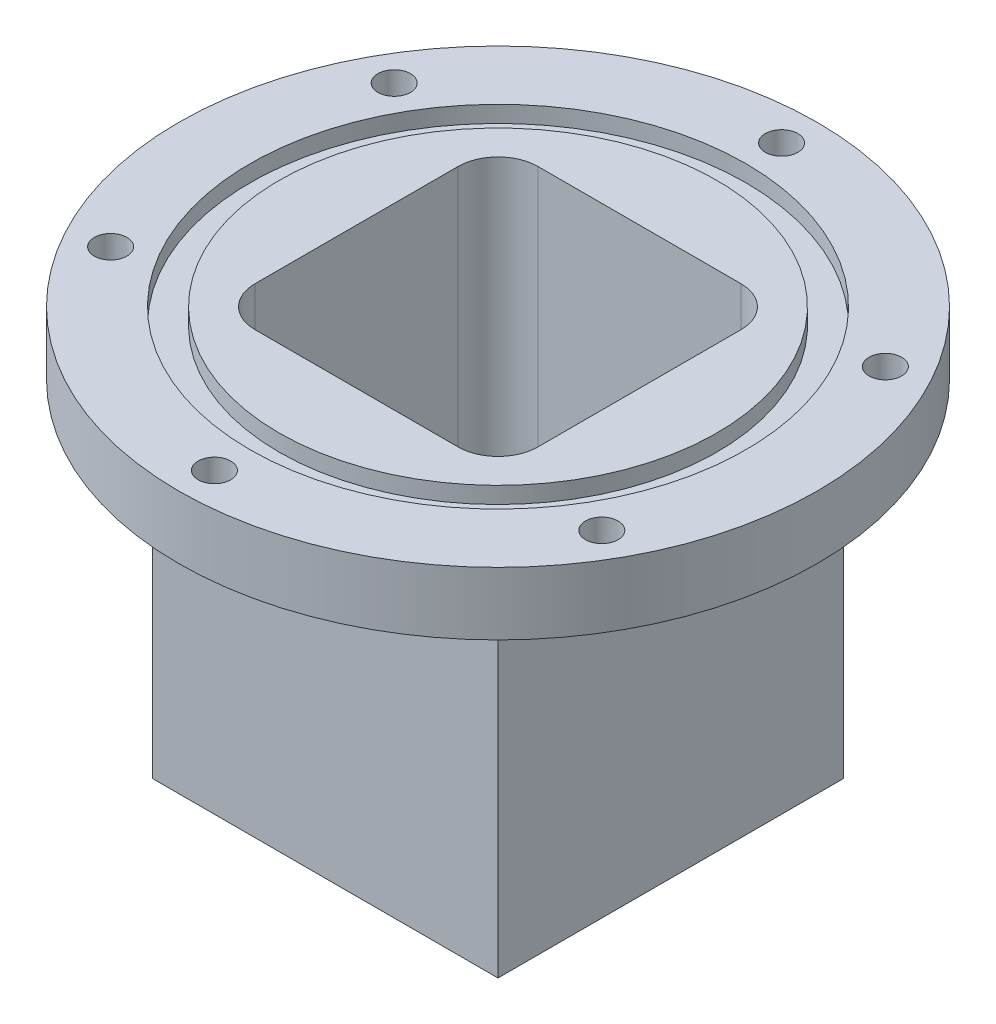
SolidWorks part; units mm, degrees
note: '?' marks a value the reader was unsure of. The reader was unsure of these and kept them because the rebuilt part matched: shared geometry of "Sketch1<3>".
ref_plane "Front Plane" through (0, 0, 0) normal (0, 0, 1) x (1, 0, 0)
ref_plane "Top Plane" through (0, 0, 0) normal (0, 1, 0) x (1, 0, 0)
ref_plane "Right Plane" through (0, 0, 0) normal (1, 0, 0) x (0, 0, -1)
ref_axis "Axis1" through (0, 47.5, 0) along (0, -1, 0)?
sketch "Sketch1" plane through (0, 0, 0) normal (0, 1, 0) x (1, 0, 0)
  line L0 (27.5, 27.5) -> (-27.5, 27.5)
  line L1 (22.5, -22.5) -> (-22.5, -22.5)
  line L2 (22.5, -22.5) -> (22.5, 22.5)
  line L3 (22.5, 22.5) -> (-22.5, 22.5)
  line L4 (-22.5, -22.5) -> (-22.5, 22.5)
  line L5 (22.5, -22.5) -> (-22.5, 22.5) construction
  line L6 (22.5, 22.5) -> (-22.5, -22.5) construction
  line L7 (-27.5, -27.5) -> (-27.5, 27.5)
  line L8 (27.5, -27.5) -> (-27.5, -27.5)
  line L9 (27.5, -27.5) -> (27.5, 27.5)
  point P0 (0, 0)
  dimension "D1" = 45
  dimension "D2" = 5
extrude "Boss-Extrude1" add sketch "Sketch1" against normal blind 5 contours L4 L1 L2 L3 | L8 L9 L0 L7 L1 L4 L3 L2
extrude "Boss-Extrude2" add sketch "Sketch1<3>" along normal blind 60 contours L8 L9 L0 L7 L1 L4 L3 L2
sketch "Sketch1<3>" plane through (0, 0, 0) normal (0, 1, 0) x (1, 0, 0) same geometry as "Sketch1"
sketch "Sketch6" plane through (0, 60, 0) normal (0, 1, 0) x (1, 0, 0)
  line L1 (35.921, -35.921) -> (-35.921, -35.921) construction
  line L2 (35.921, -35.921) -> (35.921, 35.921) construction
  line L3 (35.921, 35.921) -> (-35.921, 35.921) construction
  line L4 (-35.921, -35.921) -> (-35.921, 35.921) construction
  line L5 (35.921, -35.921) -> (-35.921, 35.921) construction
  line L6 (35.921, 35.921) -> (-35.921, -35.921) construction
  line L11 (-27.5, -27.5) -> (27.5, -27.5)
  line L12 (27.5, -27.5) -> (27.5, 27.5)
  line L13 (27.5, 27.5) -> (-27.5, 27.5)
  line L14 (-27.5, 27.5) -> (-27.5, -27.5)
  line L15 (-27.5, -27.5) -> (27.5, -27.5)
  line L16 (27.5, -27.5) -> (27.5, 27.5)
  line L17 (27.5, 27.5) -> (-27.5, 27.5)
  line L18 (-27.5, 27.5) -> (-27.5, -27.5)
  circle A0 centre (0, 0) radius 50.8
  point P0 (0, 0)
  line M7 (-27.5, -27.5) -> (27.5, -27.5)
  line M8 (27.5, -27.5) -> (27.5, 27.5)
  line M9 (27.5, 27.5) -> (-27.5, 27.5)
  line M10 (-27.5, 27.5) -> (-27.5, -27.5)
  dimension "D1" = 101.6
  dimension "D2" = 0
extrude "Boss-Extrude4" add sketch "Sketch6" against normal blind 10 contours A0 M7 M10 M9 M8 | L2 L3 L4 L1
sketch "Sketch7" plane through (0, -5, 0) normal (0, -1, 0) x (1, 0, 0)
  circle A0 centre (0, 0) radius 12
  dimension "D1" = 24
extrude "Boss-Extrude5" add sketch "Sketch7" along normal blind 10 contours A0
hole_wizard "#6 (0.204) Diameter Hole2" positions "Sketch9" profile "Sketch10" hole size "#6" standard "ANSI Inch"
sketch "Sketch9" plane through (0, -15, 0) normal (0, -1, 0) x (-1, 0, 0)
  point P0 (0, 0)
sketch "Sketch10" plane through (0, -15, 0) normal (1, 0, 0) x (0, 0, -1)
  line L0 (0, 0) -> (0, 16.5557)
  line L1 (0, 16.5557) -> (2.5908, 14.999)
  line L2 (2.5908, 14.999) -> (2.5908, 0)
  line L5 (2.5908, 0) -> (0, 0)
  line L10 (0, 16.5557) -> (-2.5908, 14.999) construction
  line L11 (0, -6.35) -> (0, 107.95) construction
  dimension "Hole Dia." = 5.1816
  dimension "Hole Depth" = 14.999
  dimension "Drill Angle" = 118
sketch "Sketch11" plane through (0, -15, 0) normal (0, -1, 0) x (1, 0, 0)
  circle A0 centre (0, 0) radius 7
  circle A1 centre (0, 0) radius 12 construction
  dimension "D1" = 5
extrude "Cut-Extrude1" cut sketch "Sketch11" against normal up to surface (10 mm away) up to face at (0, -5, 12)
sketch "Sketch13" plane through (0, 60, 0) normal (0, 1, 0) x (1, 0, 0)
  circle A0 centre (0, 0) radius 31.8198 construction
  circle A1 centre (0, 0) radius 39.4398
  circle A2 centre (0, 0) radius 34.8198
  dimension "D1" = 3
  dimension "D2" = 4.62
extrude "Cut-Extrude3" cut sketch "Sketch13" against normal blind 2.64 contours A1 A2
fillet "Fillet2" radius 6.35 4 edges at (22.5, 30, -22.5) (22.5, 30, 22.5) (-22.5, 30, -22.5) (-22.5, 30, 22.5)
hole_wizard "#6 (0.204) Diameter Hole1" positions "Sketch15" profile "Sketch14" hole size "#6" standard "ANSI Inch" end condition through all
sketch "Sketch15" plane through (0, 60, 0) normal (0, 1, 0) x (1, 0, 0)
  line L0 (0, 0) -> (-39.075, -22.56) construction
  line L2 (0, 0) -> (-45.1199, 0) construction
  circle A0 centre (0, 0) radius 45.1199 construction
  circle A1 centre (0, 0) radius 50.8 construction
  circle A3 centre (0, 0) radius 50.8 construction
  circle A4 centre (0, 0) radius 39.4398 construction
  circle A5 centre (0, 0) radius 39.4398 construction
  point P0 (-39.075, -22.56)
  dimension "D1" = 101.6
  dimension "D3" = 78.8796
  dimension "D4" = 90.2398
  dimension "D2" = 30
sketch "Sketch14" plane through (-39.075, 60, 22.56) normal (1, 0, 0) x (0, 0, 1)
  line L0 (0, 0) -> (0, 75)
  line L1 (0, 75) -> (2.5908, 75)
  line L2 (2.5908, 75) -> (2.5908, 0)
  line L5 (2.5908, 0) -> (0, 0)
  line L11 (0, -6.35) -> (0, 107.95) construction
  dimension "Thru Hole Dia." = 5.1816
  dimension "Thru Hole Depth" = 75
pattern_circular "CirPattern2" count 6 over 360 about axis through (0, 0, 0) along (0, 1, 0) of "#6 (0.204) Diameter Hole1"
equation "\"D4@Sketch15\"=(\"D1@Sketch15\"-\"D3@Sketch15\")/2+\"D3@Sketch15\""
